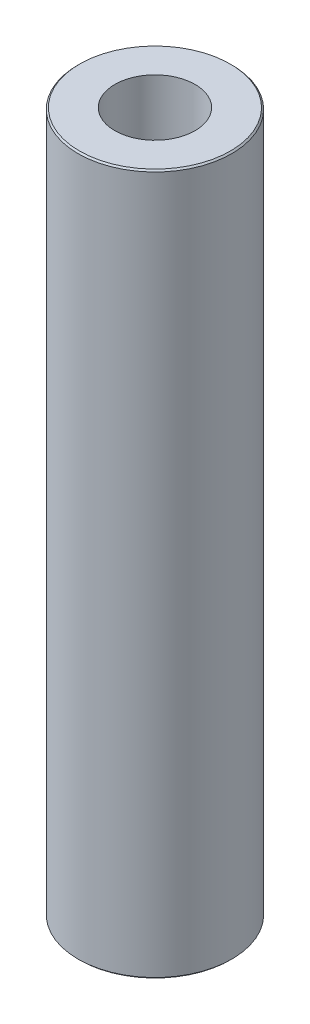
SolidWorks part; units mm, degrees
ref_plane "Front Plane" through (0, 0, 0) normal (0, 0, 1) x (1, 0, 0)
ref_plane "Top Plane" through (0, 0, 0) normal (0, 1, 0) x (1, 0, 0)
ref_plane "Right Plane" through (0, 0, 0) normal (1, 0, 0) x (0, 0, -1)
sketch "Sketch1" plane through (0, 0, 0) normal (0, 1, 0) x (1, 0, 0)
  circle A0 centre (0, 0) radius 52.5
  dimension "SHAFT_OD" = 105
extrude "Boss-Extrude1" add sketch "Sketch1" along normal blind 478.452
sketch "Sketch2" plane through (0, 0, 0) normal (0, 1, 0) x (1, 0, 0)
  circle A0 centre (0, 0) radius 27.3942
  dimension "BORE_D" = 54.7884
extrude "Cut-Extrude1" cut sketch "Sketch2" along normal through all
chamfer "Chamfer1" distance 1.0116 angle 45 2 edges at (0, 478.452, 52.5) (0, 0, 52.5)
